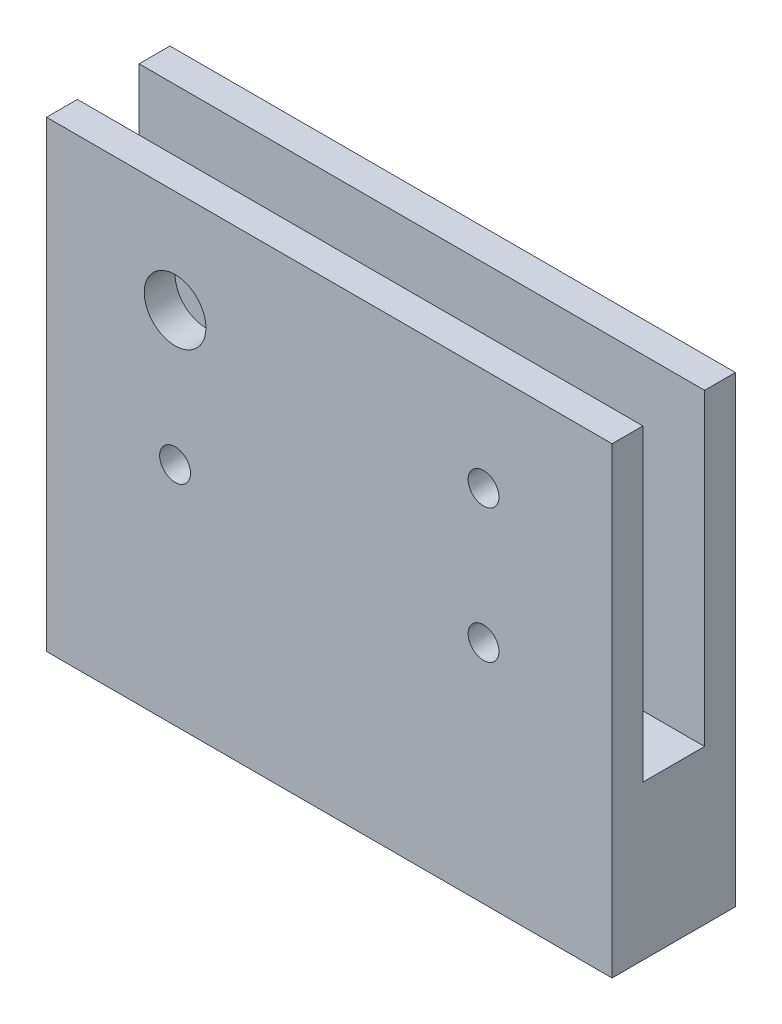
SolidWorks part; units mm, degrees
ref_plane "前视基准面" through (0, 0, 0) normal (0, 0, 1) x (1, 0, 0)
ref_plane "上视基准面" through (0, 0, 0) normal (0, 1, 0) x (1, 0, 0)
ref_plane "右视基准面" through (0, 0, 0) normal (1, 0, 0) x (0, 0, -1)
other "Configuration Table"
sketch "草图1" plane through (0, 0, 0) normal (0, 0, 1) x (1, 0, 0)
  line L1 (27.5, -22.5) -> (-27.5, -22.5)
  line L2 (27.5, -22.5) -> (27.5, 22.5)
  line L3 (27.5, 22.5) -> (-27.5, 22.5)
  line L4 (-27.5, -22.5) -> (-27.5, 22.5)
  line L5 (27.5, -22.5) -> (-27.5, 22.5) construction
  line L6 (27.5, 22.5) -> (-27.5, -22.5) construction
  point P0 (0, 0)
  dimension "D1" = 45
  dimension "D2" = 55
extrude "凸台-拉伸1" add sketch "草图1" along normal blind 12
sketch "草图2" plane through (-27.5, 0, 0) normal (-1, 0, 0) x (0, 0, 1)
  line L0 (6, 22.5) -> (6, -22.5) construction
  line L1 (12, 22.5) -> (0, 22.5) construction
  line L2 (12, -22.5) -> (0, -22.5) construction
  line L4 (9, -7.5) -> (3, -7.5)
  line L5 (9, -7.5) -> (9, 22.5)
  line L6 (9, 22.5) -> (3, 22.5)
  line L7 (3, -7.5) -> (3, 22.5)
  line L8 (9, -7.5) -> (3, 22.5) construction
  line L9 (9, 22.5) -> (3, -7.5) construction
  point P6 (6, 7.5)
  dimension "D1" = 30
  dimension "D2" = 6
extrude "切除-拉伸1" cut sketch "草图2" against normal through all
sketch "草图3" plane through (0, 0, 12) normal (0, 0, 1) x (1, 0, 0)
  line L0 (0, 22.5) -> (0, -22.5) construction
  line L1 (27.5, 22.5) -> (-27.5, 22.5) construction
  line L2 (-27.5, -22.5) -> (27.5, -22.5) construction
  line L3 (0, 12.5) -> (15, 12.5) construction
  line L4 (0, 12.5) -> (-15, 12.5) construction
  circle A0 centre (-15, 12.5) radius 3
  circle A1 centre (15, 12.5) radius 1.5
  dimension "D3" = 6
  dimension "D4" = 3
  dimension "D1" = 15
  dimension "D2" = 10
extrude "切除-拉伸2" cut sketch "草图3" against normal through all
sketch "草图4" plane through (0, 0, 12) normal (0, 0, 1) x (1, 0, 0)
  line L0 (-15, 12.5) -> (-15, -0.5) construction
  line L1 (15, 12.5) -> (15, -0.5) construction
  circle A0 centre (-15, -0.5) radius 1.5
  circle A1 centre (15, -0.5) radius 1.5
  dimension "D2" = 3
  dimension "D1" = 13
extrude "切除-拉伸3" cut sketch "草图4" against normal through all
